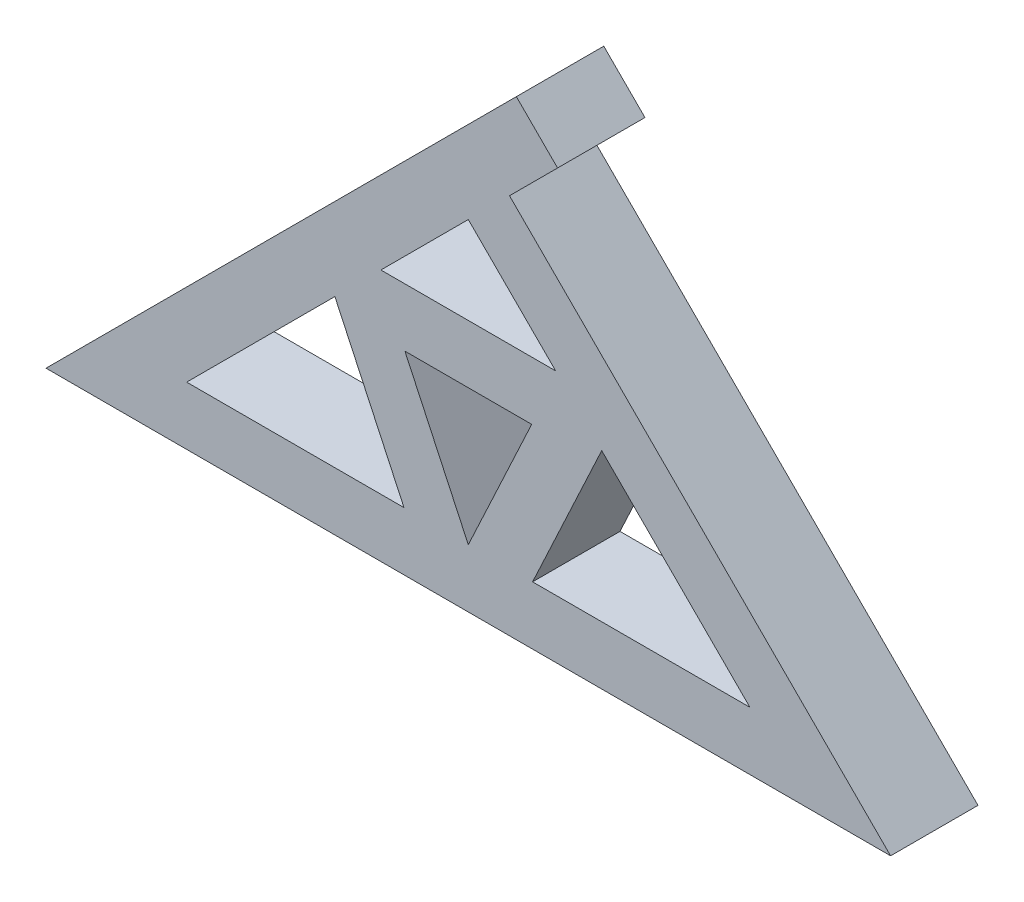
SolidWorks part; units mm, degrees
ref_plane "Front Plane" through (0, 0, 0) normal (0, 0, 1) x (1, 0, 0)
ref_plane "Top Plane" through (0, 0, 0) normal (0, 1, 0) x (1, 0, 0)
ref_plane "Right Plane" through (0, 0, 0) normal (1, 0, 0) x (0, 0, -1)
sketch "Sketch1" plane through (0, 0, 0) normal (0, 0, 1) x (1, 0, 0)
  line L0 (0, 0) -> (86.9741, 0)
  line L1 (86.9741, 0) -> (43.4871, 43.4871)
  line L2 (43.4871, 43.4871) -> (0, 0)
  line L3 (14.4853, 6) -> (43.4871, 35.0018)
  line L4 (43.4871, 35.0018) -> (72.4889, 6)
  line L5 (72.4889, 6) -> (14.4853, 6)
  line L6 (29.7491, 21.2639) -> (36.8668, 6)
  line L7 (34.4871, 26.0018) -> (52.4871, 26.0018)
  line L8 (57.225, 21.2639) -> (50.1073, 6)
  line L9 (43.4871, 6) -> (36.9579, 20.0018)
  line L10 (36.9579, 20.0018) -> (50.0162, 20.0018)
  line L11 (50.0162, 20.0018) -> (43.4871, 6)
  line L12 (43.4871, 6) -> (43.4871, 35.0018) construction
  dimension "D1" = 61.5
  dimension "D2" = 45
  dimension "D3" = 45
  dimension "D4" = 6
  dimension "D5" = 6
  dimension "D6" = 6
  dimension "D7" = 65
  dimension "D8" = 65
  dimension "D9" = 6
  dimension "D10" = 6
  dimension "D11" = 6
  dimension "D12" = 9
extrude "Boss-Extrude1" add sketch "Sketch1" along normal blind 9 contours L12 L10 L11 L5 L8 L4 L7 | L10 L12 L7 L3 L6 L5 L9 | L1 L2 L0 L4 L5 L3 region at (22.4311, 21.0559, 0) region at (37.1631, 17.2411, 0) region at (49.811, 17.2411, 0)
sketch "Sketch2" plane through (0, 0, 0) normal (-0.7071, 0.7071, 0) x (0, 0, 1)
  line L0 (4.5, 0) -> (4.5, 61.5) construction
  line L1 (9, 0) -> (0, 0) construction
  line L2 (9, 61.5) -> (0, 61.5) construction
  line L3 (0, 61.5) -> (0, 68.5)
  line L4 (0, 68.5) -> (9, 68.5)
  line L5 (9, 68.5) -> (9, 61.5)
  line L6 (4.5, 61.5) -> (4.5, 65) construction
  circle A0 centre (4.5, 65) radius 1.625
  circle A1 centre (4.5, 9) radius 1.625
  dimension "D1" = 3.25
  dimension "D3" = 3.5
  dimension "D4" = 3.25
  dimension "D2" = 7
  dimension "D5" = 9
extrude "Cut-Extrude3" cut sketch "Sketch2" against normal blind 9 contours A1 region at (6.364, 6.364, 4.5)
sketch "Sketch8" plane through (0, 0, 0) normal (-0.7071, 0.7071, 0) x (0, 0, 1)
  line L0 (4.5, 0) -> (4.5, 61.5) construction
  line L1 (0, 61.5) -> (0, 68.5)
  line L2 (0, 68.5) -> (9, 68.5)
  line L3 (9, 68.5) -> (9, 61.5)
  line L4 (4.5, 61.5) -> (4.5, 65) construction
  line L5 (9, 0) -> (0, 0) construction
  line L6 (9, 61.5) -> (0, 61.5) construction
  circle A0 centre (4.5, 65) radius 1.625
  circle A1 centre (4.5, 4) radius 1.625
  point P10 (4.5, 0)
  point P13 (4.5, 4)
  point P14 (0, 61.5)
  point P16 (9, 61.5)
  point P18 (4.5, 61.5)
  line M6 (9, 61.5) -> (0, 61.5)
  dimension "D1" = 3.25
  dimension "D4" = 3.25
  dimension "D2" = 7
  dimension "D3" = 3.5
  dimension "D5" = 4
extrude "Boss-Extrude2" add sketch "Sketch8" against normal blind 6 contours L3 L2 L1 A0 M6 region at (45.9619, 45.9619, 0.114)
sketch "Sketch9" plane through (4.2426, -4.2426, 0) normal (0.7071, -0.7071, 0) x (0, 0, -1)
  circle A0 centre (-4.5, 65) radius 2.875
  circle A2 centre (-4.5, 9) radius 2.875
  point P3 (-4.5, 4)
  dimension "D1" = 5.75
  dimension "D2" = 5.75
extrude "Cut-Extrude4" cut sketch "Sketch9" against normal blind 3 and the other way blind 33
